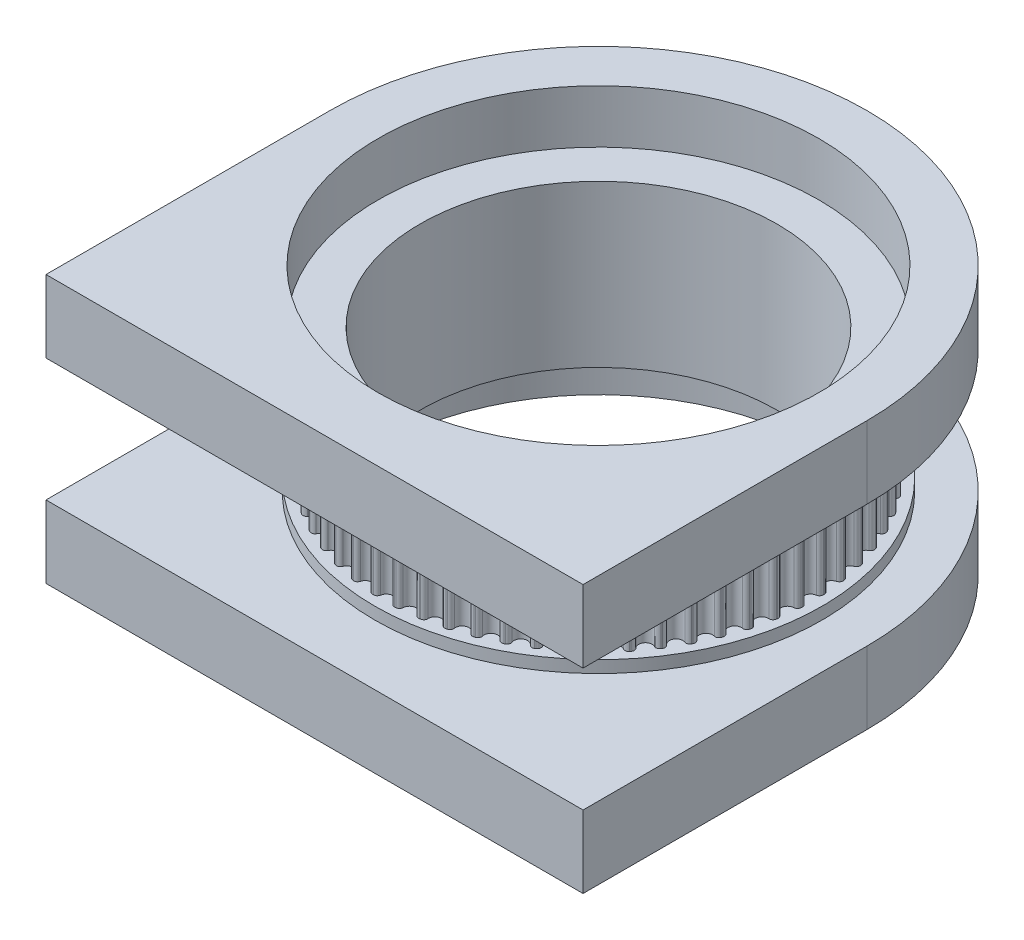
SolidWorks part; units mm, degrees
ref_plane "Front Plane" through (0, 0, 0) normal (0, 0, 1) x (1, 0, 0)
ref_plane "Top Plane" through (0, 0, 0) normal (0, 1, 0) x (1, 0, 0)
ref_plane "Right Plane" through (0, 0, 0) normal (1, 0, 0) x (0, 0, -1)
sketch "Sketch1" plane through (0, 0, 0) normal (0, 1, 0) x (1, 0, 0)
  line L0 (0, 0) -> (0, 28.2667) construction
  line L1 (0, 0) -> (2.9202, 27.7837) construction
  circle A0 centre (0, 0) radius 28.2667 construction
  circle A1 centre (0, 0) radius 27.0467 construction
  circle A2 centre (0, 27.9367) radius 0.89 construction
  circle A5 centre (2.9202, 27.7837) radius 0.89 construction
  arc A6 (0, 27.0467) -> (0.8804, 27.8061) centre (0, 27.9367) ccw
  arc A7 (0.8804, 27.8061) -> (1.3997, 28.2321) centre (1.3749, 27.7327) cw
  arc A8 (1.559, 28.2237) -> (2.031, 27.7458) centre (1.5314, 27.7245) cw
  arc A9 (2.8272, 26.8986) -> (2.031, 27.7458) centre (2.9202, 27.7837) cw
  arc A10 (1.3997, 28.2321) -> (1.559, 28.2237) centre (0, 0) cw
  arc A11 (0, 27.0467) -> (2.8272, 26.8986) centre (0, 0) ccw
  dimension "D1" = 56.5335
  dimension "D3" = 1.78
  dimension "D4" = 0.5
  dimension "D2" = 1.22
  dimension "D5" = 6
extrude "Boss-Extrude1" add sketch "Sketch1" along normal mid plane 13 contours A6 A11 A9 A8 A7 region at (0.001, 0, -0.0192)
ref_axis "Axis1" through (0, 3.3, 0) along (0, -1, 0)
pattern_circular "CirPattern1" count 60 over 360 about axis through (0, 3.3, 0) along (0, -1, 0) of "Boss-Extrude1"
sketch "Sketch2" plane through (0, 0, 0) normal (1, 0, 0) x (0, 0, -1)
  line L10 (0, 6.5) -> (29.4415, 6.5) construction
  line L11 (0, 6.5) -> (0, 8.0875) construction
  line L12 (0, 8.0875) -> (29.4415, 8.0875) construction
  line L15 (29.4415, 6.5) -> (29.4415, 8.0875) construction
  line L20 (0, 3.3) -> (0, -3.3) construction
  line L22 (29.4415, 8.0875) -> (0, 8.0875)
  line L23 (29.4415, 8.0875) -> (29.4415, 6.5)
  line L24 (29.4415, 6.5) -> (0, 6.5)
  line L25 (0, 8.0875) -> (0, 6.5)
  dimension "D1" = 1.5875
  dimension "D2" = 29.4415
  dimension "D3" = 6.5
revolve "Revolve3" add sketch "Sketch2" angle 360 about axis through (0, 3.3, 0) along (0, -1, 0) region at (0, 7.2937, -14.7207)
mirror "Mirror1" about plane through (0, 0, 0) normal (0, 1, 0) of "Revolve3"
sketch "Sketch4" plane through (0, 8.0875, 0) normal (0, 1, 0) x (1, 0, 0)
  line L0 (-35.35, 0) -> (-35.35, -37.379)
  line L1 (-35.35, -37.379) -> (35.35, -37.379)
  line L2 (35.35, -37.379) -> (35.35, 0)
  line L3 (0, -29.4415) -> (0, -37.379) construction
  arc A0 (-35.35, 0) -> (35.35, 0) centre (0, 0) cw
  circle A1 centre (0, 0) radius 29.4415 construction
  circle A3 centre (0, 0) radius 29 construction
  dimension "D2" = 58
  dimension "D3" = 6.35
  dimension "D1" = 7.9375
extrude "Boss-Extrude3" add sketch "Sketch4" along normal blind 9.525
sketch "Sketch9" plane through (0, 17.6125, 0) normal (0, 1, 0) x (1, 0, 0)
  circle A0 centre (0, 0) radius 29
  dimension "D1" = 58
extrude "Cut-Extrude2" cut sketch "Sketch9" against normal blind 7
mirror "Mirror5" about plane through (0, 0, 0) normal (0, 1, 0) of "Cut-Extrude2", "Boss-Extrude3"
sketch "Sketch10" plane through (0, 0, 0) normal (0, 1, 0) x (1, 0, 0)
  circle A0 centre (0, 0) radius 23.5
  dimension "D1" = 47
extrude "Cut-Extrude3" cut sketch "Sketch10" against normal through all both and the other way through all
ref_axis "Axis2" through (0, 0, -38.9864) along (0, 0, 1)
equation "\"TEETH_NUM\"= 60"
equation "\"TOOTH_PITCH\"= 3mm"
equation "\"PITCH_LINE_OFFSET\"= .015in"
equation "\"DIAMETER_PER_GROOVE\"= \"OUTSIDE_DIAMETER\" / \"TEETH_NUM\" * 1in"
equation "\"PITCH_DIAMETER\"= ( ( \"TEETH_NUM\" * 3 - 1.31 ) / 3.1415 + .415 ) * 1mm"
equation "\"OUTSIDE_DIAMETER\"= \"PITCH_DIAMETER\" - \"PITCH_LINE_OFFSET\" * 2"
equation "\"D1@Sketch1\"=\"OUTSIDE_DIAMETER\""
equation "\"TOOTH_HEIGHT\"= 1.22mm"
equation "\"D2@Sketch1\"=\"TOOTH_HEIGHT\""
equation "\"TOOTH_DIAMETER\"= 1.78mm"
equation "\"INTERNAL_RADIUS\"= .5mm"
equation "\"D3@Sketch1\"=\"TOOTH_DIAMETER\""
equation "\"D5@Sketch1\"=360 / \"TEETH_NUM\""
equation "\"D4@Sketch1\"=\"INTERNAL_RADIUS\""
equation "\"D1@CirPattern1\"=\"TEETH_NUM\""
equation "\"BELT_GAP\"= 13mm"
equation "\"D2@Sketch2\"=\"PITCH_DIAMETER\"/2+1/32"
equation "\"D3@Sketch2\"=\"BELT_GAP\"/2"
equation "\"D1@Boss-Extrude1\"=\"BELT_GAP\""
